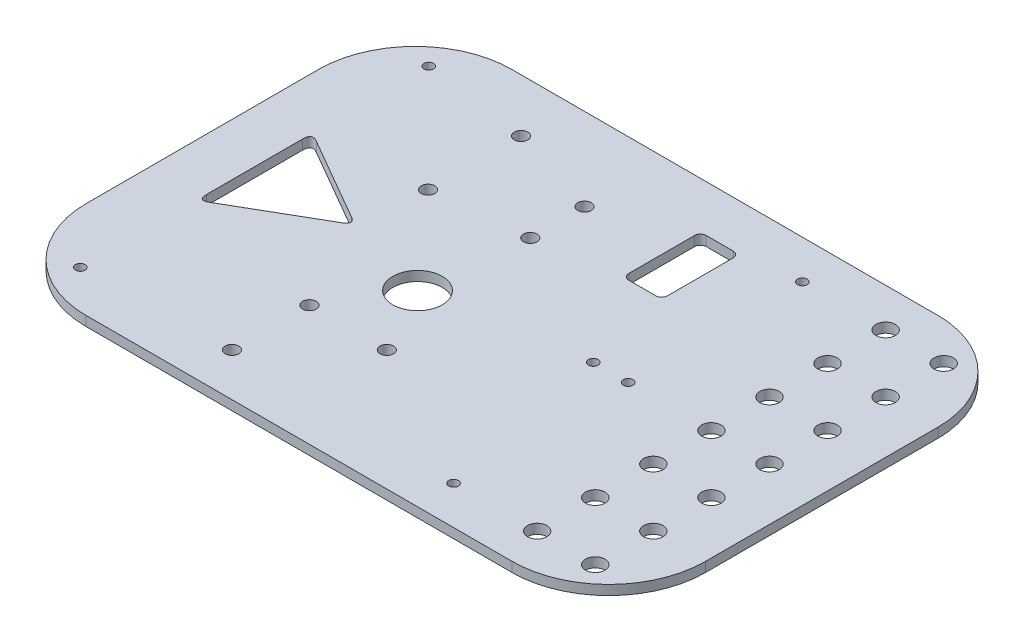
SolidWorks part; units mm, degrees
ref_plane "Front Plane" through (0, 0, 0) normal (0, 0, 1) x (1, 0, 0)
ref_plane "Top Plane" through (0, 0, 0) normal (0, 1, 0) x (1, 0, 0)
ref_plane "Right Plane" through (0, 0, 0) normal (1, 0, 0) x (0, 0, -1)
sketch "Sketch1" plane through (0, 0, 0) normal (0, 1, 0) x (1, 0, 0)
  line L2 (-160, 110) -> (160, 110)
  line L3 (-160, 110) -> (-160, -110)
  line L4 (-160, -110) -> (160, -110)
  line L5 (160, 110) -> (160, -110)
  line L6 (-160, 110) -> (160, -110) construction
  line L7 (-160, -110) -> (160, 110) construction
  point P3 (0, 0)
  dimension "D1" = 320
  dimension "D2" = 220
extrude "the upper chasiss" add sketch "Sketch1" along normal mid plane 5 contours L3 L2 L5 L4
sketch "Sketch2" plane through (0, 0, 0) normal (0, 1, 0) x (1, 0, 0)
  line L0 (160, 0) -> (-160, 0) construction
  line L1 (160, 110) -> (160, -110) construction
  line L2 (-160, 110) -> (-160, -110) construction
  circle A0 centre (60, 0) radius 2.5
  circle A1 centre (42, 0) radius 2.5
  dimension "D1" = 5
  dimension "D2" = 5
  dimension "D3" = 18
  dimension "D4" = 100
extrude "Battary" cut sketch "Sketch2" along normal up to surface and the other way up to surface up to face at (0, 2.5, 0) other way up to face at (0, -2.5, 0)
sketch "Sketch3" plane through (0, 0, 0) normal (0, 1, 0) x (1, 0, 0)
  line L1 (-56.8984, -47.7601) -> (-16.8984, -47.7601) construction
  line L2 (-56.8984, -47.7601) -> (-56.8984, -87.7601) construction
  circle A0 centre (-56.8984, -47.7601) radius 3.5
  circle A1 centre (-16.8984, -47.7601) radius 3.5
  circle A2 centre (-56.8984, -87.7601) radius 3.5
  dimension "D1" = 7
  dimension "D2" = 7
  dimension "D3" = 7
  dimension "D4" = 40
  dimension "D5" = 40
extrude "power section" cut sketch "Sketch3" against normal up to surface and the other way up to surface up to face at (60, -2.5, -2.5) other way up to face at (60, 2.5, -2.5)
sketch "arduino" plane through (0, 0, 0) normal (0, 1, 0) x (1, 0, 0)
  line L0 (-77.9335, 82.5888) -> (-77.9335, 34.5888) construction
  line L1 (-77.9335, 34.5888) -> (-29.9335, 39.3888) construction
  line L2 (-29.9335, 39.3888) -> (-29.9335, 67.3888) construction
  line L3 (-29.9335, 67.3888) -> (-77.9335, 82.5888) construction
  circle A0 centre (-77.9335, 82.5888) radius 3.5
  circle A1 centre (-77.9335, 34.5888) radius 3.5
  circle A2 centre (-29.9335, 67.3888) radius 3.5
  circle A3 centre (-29.9335, 39.3888) radius 3.5
  dimension "D1" = 7
  dimension "D2" = 7
  dimension "D3" = 7
  dimension "D4" = 7
  dimension "D5" = 48
  dimension "D6" = 28
  dimension "D7" = 48
  dimension "D8" = 15.2
extrude "arduino section" cut sketch "arduino" against normal mid plane 5
sketch "Sketch7" plane through (0, 2.5, 0) normal (0, 1, 0) x (1, 0, 0)
  line L0 (-160, 0) -> (160, 0) construction
  line L1 (-160, 110) -> (-160, -110) construction
  line L2 (160, 110) -> (160, -110) construction
  line L3 (0, 110) -> (0, -110) construction
  line L4 (-160, 110) -> (160, 110) construction
  line L5 (-160, -110) -> (160, -110) construction
  line L6 (-133, -90) -> (-133, 0) construction
  line L7 (-133, 90) -> (-133, 0) construction
  line L8 (60, 90) -> (60, -90.1777) construction
  circle A2 centre (-133, -90) radius 2.5
  circle A3 centre (-133, 90) radius 2.5
  circle A4 centre (60, -90.1777) radius 2.5
  circle A5 centre (60, 90) radius 2.5
  dimension "D1" = 5
  dimension "D2" = 5
  dimension "D5" = 5
  dimension "D6" = 5
  dimension "D3" = 20
  dimension "D4" = 27
  dimension "D7" = 100
extrude "link nails" cut sketch "Sketch7" against normal mid plane 10
sketch "Sketch9" plane through (0, 2.5, 0) normal (0, 1, 0) x (1, 0, 0)
  line L0 (160, 0) -> (-160, 0) construction
  line L1 (160, 110) -> (160, -110) construction
  line L2 (-160, 110) -> (-160, -110) construction
  line L4 (11.3906, 85.9212) -> (31.3906, 85.9212)
  line L5 (11.3906, 85.9212) -> (11.3906, 45.9212)
  line L6 (11.3906, 45.9212) -> (31.3906, 45.9212)
  line L7 (31.3906, 85.9212) -> (31.3906, 45.9212)
  line L8 (11.3906, 85.9212) -> (31.3906, 45.9212) construction
  line L9 (11.3906, 45.9212) -> (31.3906, 85.9212) construction
  point P6 (126.2109, 0)
  dimension "D1" = 20
  dimension "D2" = 40
extrude "rect cut" cut sketch "Sketch9" against normal mid plane 10
sketch "Sketch10" plane through (0, 2.5, 0) normal (0, 1, 0) x (1, 0, 0)
  circle A0 centre (-35.5184, -13.2763) radius 12.759
extrude "circ cut" cut sketch "Sketch10" against normal mid plane 10
fillet "Fillet4" radius 50 4 edges at (-160, 0, 110) (160, 0, 110) (160, 0, -110) (-160, 0, -110) first distance on face at (0, 0, 110) first distance on face at (0, 0, -110)
sketch "Sketch11" plane through (0, 0, 0) normal (0, 1, 0) x (1, 0, 0)
  line L6 (-133, 90) -> (197.2842, 90) construction
  line L7 (-110, 110) -> (110, 110) construction
  line L9 (160, 60) -> (160, -60) construction
  line L10 (-133, -90) -> (197.2842, -90) construction
  circle A2 centre (133, 90) radius 5
  dimension "D1" = 20
  dimension "D2" = 10
  dimension "D3" = 27
extrude "Cut-Extrude1" cut sketch "Sketch11" against normal mid plane 10
pattern_linear "LPattern1" count 7 spacing 30 along (0, 0, 1) count 2 spacing 30 along (-1, 0, 0) of "Cut-Extrude1"
fillet "Fillet5" radius 3 4 edges at (11.3906, 0, -45.9212) (31.3906, 0, -45.9212) (11.3906, 0, -85.9212) (31.3906, 0, -85.9212)
sketch "Sketch13" plane through (0, 0, 0) normal (0, 1, 0) x (1, 0, 0)
  line L0 (-133, 90) -> (-133, -90) construction
  line L1 (-160, 0) -> (160, 0) construction
  line L2 (-160, 60) -> (-160, -60) construction
  line L3 (160, 60) -> (160, -60) construction
  line L4 (-133, 30) -> (-81.0385, 0)
  line L5 (-81.0385, 0) -> (-133, -30)
  line L6 (-133, -30) -> (-133, 30)
  dimension "D1" = 60
extrude "Cut-Extrude2" cut sketch "Sketch13" against normal mid plane 10
fillet "Fillet6" radius 3 3 edges at (-133, 0, 30) (-81.0385, 0, 0) (-133, 0, -30) curvature continuous yes
equation "\"carWidth\"= 22cm'the car full width"
equation "\"carLong\"= 32cm"
equation "\"D2@Sketch1\"=\"carWidth\""
equation "\"D1@Sketch1\"=\"carLong\""
equation "\"chasissTheikness\"= 0.5cm"
equation "\"D1@the upper chasiss\"=\"chasissTheikness\" "
equation "\"battaryMargin\"= 1.8cm'the width between the two battary nails"
equation "\"battaryNailsDiam\" = 5mm'battary Nails Diameters"
equation "\"D1@Sketch2\"=\"battaryNailsDiam\""
equation "\"D2@Sketch2\"=\"battaryNailsDiam\""
equation "\"D3@Sketch2\"=\"battaryMargin\""
equation "\"powerWidht\"= 40mm"
equation "\"powerNailDiam\"= 7mm"
equation "\"D1@Sketch3\"=\"powerNailDiam\""
equation "\"D2@Sketch3\"=\"powerNailDiam\""
equation "\"D3@Sketch3\"=\"powerNailDiam\""
equation "\"D4@Sketch3\"=\"powerWidht\""
equation "\"D5@Sketch3\"=\"powerWidht\""
equation "\"arduinoTopWidth\" = 4.8cm'the width between nails"
equation "\"arduinoBottomWidth\"= 2.8cm'the width between nails"
equation "\"arduinoNailsDiam\"= 7mm'the nail diameter"
equation "\"D1@arduino\" = \"arduinoNailsDiam\""
equation "\"D2@arduino\" = \"arduinoNailsDiam\""
equation "\"D3@arduino\" = \"arduinoNailsDiam\""
equation "\"D4@arduino\" = \"arduinoNailsDiam\""
equation "\"D5@arduino\" = \"arduinoTopWidth\""
equation "\"D6@arduino\" = \"arduinoBottomWidth\""
equation "\"D7@arduino\" = \"arduinoTopWidth\""
equation "\"arduinoTobBottomShift\"= 15.2mm"
equation "\"D8@arduino\" = \"arduinoTobBottomShift\""
equation "\"chasissNailsDiam\"= 0.5cm"
equation "\"D2@Sketch7\"=\"chasissNailsDiam\""
equation "\"D1@Sketch7\"=\"chasissNailsDiam\""
equation "\"D5@Sketch7\"=\"chasissNailsDiam\""
equation "\"D6@Sketch7\"=\"chasissNailsDiam\""
equation "\"10ةة\"=12.1958"
